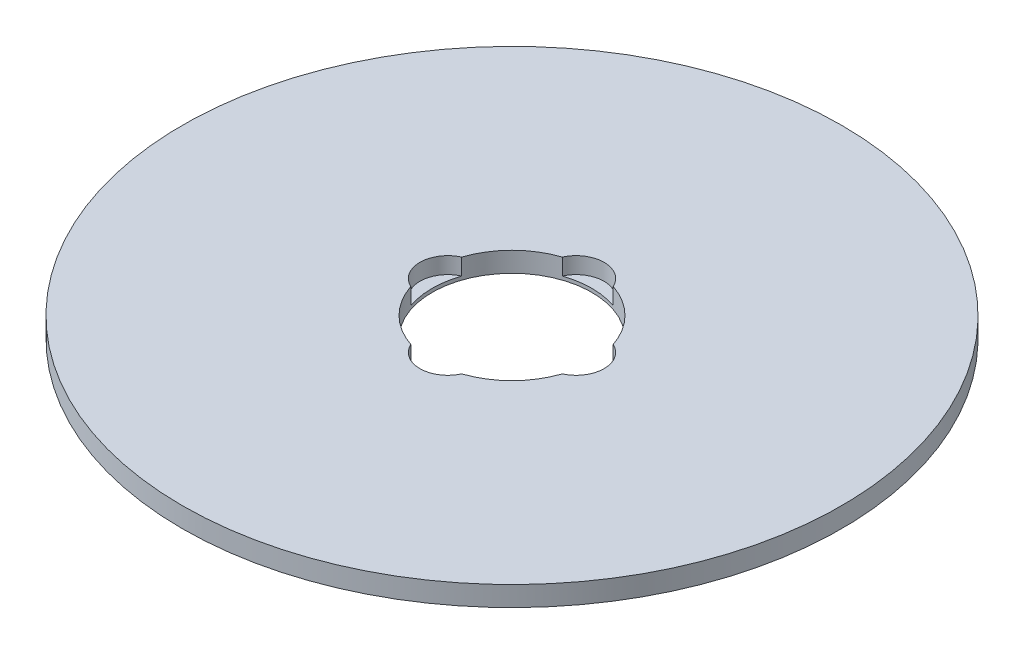
SolidWorks part; units mm, degrees
ref_plane "Front Plane" through (0, 0, 0) normal (0, 0, 1) x (1, 0, 0)
ref_plane "Top Plane" through (0, 0, 0) normal (0, 1, 0) x (1, 0, 0)
ref_plane "Right Plane" through (0, 0, 0) normal (1, 0, 0) x (0, 0, -1)
sketch "Sketch1" plane through (0, 0, 0) normal (0, 1, 0) x (1, 0, 0)
  circle A0 centre (0, 0) radius 82.5
  dimension "FLANGE_OD" = 165
extrude "Boss-Extrude1" add sketch "Sketch1" along normal blind 5
sketch "Sketch2" plane through (0, 0, 0) normal (0, 1, 0) x (1, 0, 0)
  circle A0 centre (0, 0) radius 20
  dimension "BORE_D" = 40
extrude "Cut-Extrude1" cut sketch "Sketch2" along normal through all
sketch "Sketch3" plane through (0, 5, 0) normal (0, 1, 0) x (1, 0, 0)
  circle A0 centre (0, 0) radius 16.0441 construction
  circle A1 centre (-16.0441, 0) radius 7.0081
  dimension "BOLT_D" = 14.0162
  dimension "BOLT_PCD" = 32.0882
extrude "Cut-Extrude2" cut sketch "Sketch3" against normal blind 4.1184
pattern_circular "CirPattern1" count 4 over 360 about axis through (0, 0, 0) along (0, 1, 0) of "Cut-Extrude2"
